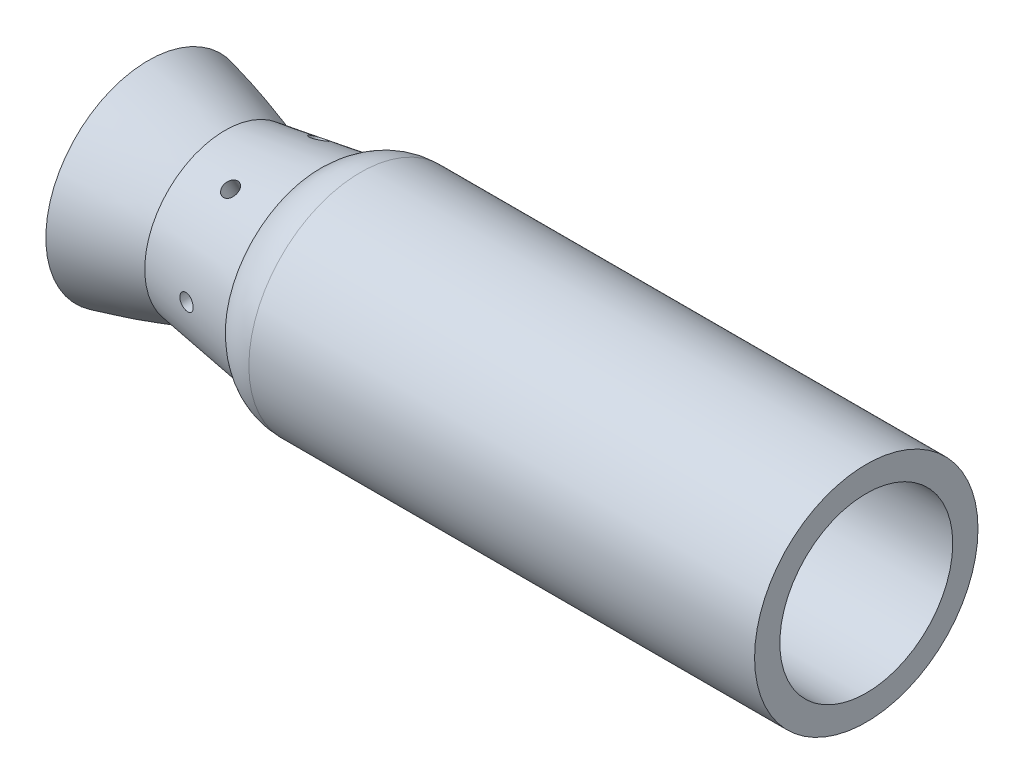
SolidWorks part; units mm, degrees
material "Thornel Mat VMA"
ref_plane "Front Plane" through (0, 0, 0) normal (0, 0, 1) x (1, 0, 0)
ref_plane "Top Plane" through (0, 0, 0) normal (0, 1, 0) x (1, 0, 0)
ref_plane "Right Plane" through (0, 0, 0) normal (1, 0, 0) x (0, 0, -1)
sketch "Sketch1" plane through (0, 0, 0) normal (0, 0, 1) x (1, 0, 0)
  line L0 (189.133, 27.386) -> (28.9492, 27.386)
  line L1 (21.8782, 24.4571) -> (13.5417, 16.1206)
  line L3 (0, 0) -> (-234.9488, 0) construction
  line L5 (16.2213, 30.1139) -> (-13.9816, 25.4377)
  line L8 (189.133, 35.386) -> (28.9492, 35.386)
  line L12 (16.2213, 30.1139) -> (7.8848, 21.7775)
  line L13 (189.133, 27.386) -> (189.133, 35.386)
  line L14 (-40.127, 24.64) -> (-38.315, 32.4321)
  arc A0 (28.9492, 27.386) -> (21.8782, 24.4571) centre (28.9492, 17.386) ccw
  arc A4 (28.9492, 35.386) -> (16.2213, 30.1139) centre (28.9492, 17.386) ccw
  arc A7 (2.3482, 19.2268) -> (2.3482, 19.2268) centre (2.3482, 19.2268) cw
  arc A8 (7.8848, 21.7775) -> (2.3482, 19.2268) centre (1.6623, 28) cw construction
  arc A9 (2.3482, 19.2268) -> (7.8848, 21.7775) centre (1.6623, 28) ccw
  arc A10 (0.1069, 11.2722) -> (0, 11.5361) centre (3.1693, 12.6659) cw construction
  arc A11 (13.5417, 16.1206) -> (0.1069, 11.2722) centre (1.6623, 28) cw construction
  arc A12 (13.5417, 16.1206) -> (1.6623, 11.2) centre (1.6623, 28) cw
  arc A13 (1.6623, 11.2) -> (0, 11.5361) centre (1.6623, 15.4784) cw
  spline S0 degree 2 poles (0, 11.5361) (-19.9483, 19.9476) (-40.127, 24.64) knots 0 0 0 1 1 1 construction
  spline S1 degree 1 poles (2.3482, 19.2268) (-38.315, 32.4321) knots 0 0 1 1 construction
  spline S2 degree 2 poles (0, 11.5361) (-19.9483, 19.9476) (-40.127, 24.64) knots 0 0 0 1 1 1
  spline S3 degree 2 poles (2.3482, 19.2268) (0.3135, 20.0775) (-5.8003, 22.5182) (-13.9784, 25.475) (-28.1602, 30.0701) (-38.315, 32.4321) knots 0.018494 0.018494 0.018494 0.117488 0.315475 0.513463 1 1 1
  dimension "D1" = 10
  dimension "D4" = 16.8
  dimension "D5" = 4.2784
  dimension "D14" = 27.386
  dimension "D16" = 167.2548
  dimension "D2" = 11.2
  dimension "D6" = 45
  dimension "D7" = 24.64
  dimension "D3" = 8
revolve "Revolve1" add sketch "Sketch1" angle 360 about L3 region at (72.719, 28.6368, 0) region at (2.2964, 24.7796, 0)
ref_plane "Plane1" through (0, 0, 40) normal (0, 0, 1) x (1, 0, 0)
sketch "Sketch2" plane through (0, 0, 40) normal (0, 0, 1) x (1, 0, 0)
  line L0 (-13.9816, 25.4377) -> (-13.9816, -25.4377) construction
  line L2 (16.2213, -30.1139) -> (16.2213, 30.1139) construction
  line L3 (-13.9816, 25.4377) -> (-13.9816, -25.4377) construction
  line L4 (-13.9816, 0) -> (16.2213, 0) construction
  line L6 (1.6623, 11.2) -> (1.6623, -11.2) construction
  circle A0 centre (1.6623, 0) radius 2.5
  dimension "D2" = 5
extrude "Cut-Extrude2" cut sketch "Sketch2" against normal blind 20 contours A0
pattern_circular "CirPattern1" count 6 over 360 about axis through (0, 0, 0) along (-1, 0, 0) of "Cut-Extrude2" reverse direction yes
equation "\"theta_t\"= 36.9009 - ( 426.271 / ( \"Aet\" + 7.00037 ) ) + ( 10026.8 / ( \"Aet\" + 7.00037 ) ^ 2 ) - ( 175410 / ( \"Aet\" + 7.00037 ) ^ 3 ) + ( ( 1.6742 * ( 10 ^ 6 ) ) / ( \"Aet\" + 7.00037 ) ^ 4 ) - ( ( 6.7643 * ( 10 ^ 6 ) ) / ( \"Aet\" + 7.00037 ) ^ 5 )"
equation "\"rt\"= 11.2"
equation "\"re\"= sqr ( \"rt\" ^ 2 * \"Aet\" )"
equation "\"Aet\"= 4.84"
equation "\"L\"= 0.8 * ( ( \"re\" / tan ( 15 ) ) - ( \"rt\" / tan ( 15 ) ) )"
equation "\"lc\"= ( \"l*\" / \"cr\" )"
equation "\"b\"= tan ( \"theta_t\" )"
equation "\"a\"= ( \"re\" - \"b\" * \"L\" - \"c\" ) / \"L\" ^ 2"
equation "\"c\"= \"rt\" * ( 1.382 - 0.382 * cos ( \"theta_t\" ) )"
equation "\"cr\"= 5.9789"
equation "\"rc\"= sqr ( \"cr\" * ( \"rt\" ^ 2 ) )"
equation "\"D14@Sketch1\"=\"rc\""
equation "\"l*\"= 1000"
equation "\"D16@Sketch1\"=\"lc\""
equation "\"th\"= 8"
equation "\"theta_cr\"= 45deg"
equation "\"theta_e\"= 5.48 + ( 134.316 / ( \"Aet\" + 1.49269 ) ) - ( 1742.02 / ( \"Aet\" + 1.49269 ) ^ 2 ) + ( 13091 / ( \"Aet\" + 1.49269 ) ^ 3 ) - ( 41929.9 / ( \"Aet\" + 1.49269 ) ^ 4 ) + ( 44445.1 / ( \"Aet\" + 1.49269 ) ^ 5 )"
equation "\"Nx\"= 0"
equation "\"Ny\"= \"c\""
equation "\"Qx\"= ( \"re\" - ( tan ( \"theta_e\" ) * \"L\" ) - \"c\" ) / ( tan ( \"theta_t\" ) - tan ( \"theta_e\" ) )"
equation "\"Qy\"= tan ( \"theta_t\" ) * \"Qx\" + \"c\""
equation "\"Ex\"= \"L\""
equation "\"Ey\"= \"re\""
equation "\"D3@Sketch1\"=\"th\""
equation "\"D2@Sketch1\"=\"rt\""
equation "\"D4@Sketch1\"=\"rt\"*1.5"
equation "\"D5@Sketch1\"=\"rt\"*0.382"
equation "\"D6@Sketch1\"=\"theta_cr\""
equation "\"D7@Sketch1\"=\"re\""
